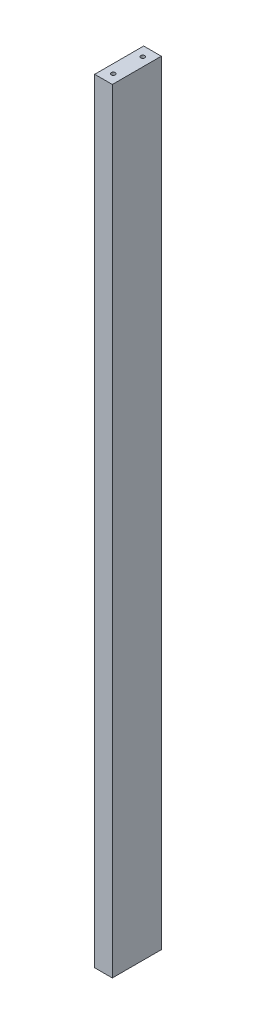
SolidWorks part; units mm, degrees
material "Beech"
ref_plane "Front Plane" through (0, 0, 0) normal (0, 0, 1) x (1, 0, 0)
ref_plane "Top Plane" through (0, 0, 0) normal (0, 1, 0) x (1, 0, 0)
ref_plane "Right Plane" through (0, 0, 0) normal (1, 0, 0) x (0, 0, -1)
sketch "Sketch1" plane through (0, 0, 0) normal (0, 1, 0) x (1, 0, 0)
  line L1 (0, 0) -> (18, 0)
  line L2 (0, 0) -> (0, 50)
  line L3 (0, 50) -> (18, 50)
  line L4 (18, 0) -> (18, 50)
  dimension "D1" = 18
  dimension "D2" = 50
extrude "base" add sketch "Sketch1" along normal blind 789.8
hole_wizard "end bolt holes for inserts" positions "Sketch2" profile "Sketch3" tap size "M5x0.8" standard "ANSI Metric"
sketch "Sketch2" plane through (0, 0, 0) normal (0, -1, 0) x (-1, 0, 0)
  line L1 (-9, 50) -> (-9, 0)
  line L2 (-18, 50) -> (0, 50) construction
  line L3 (0, 0) -> (-18, 0) construction
  line L4 (-9, 10) -> (-18, 25)
  line L5 (-18, 0) -> (-18, 50) construction
  line L6 (-18, 25) -> (-9, 40)
  point P10 (-9, 40)
  point P12 (-9, 10)
  dimension "D1" = 30
sketch "Sketch3" plane through (9, 0, -40) normal (1, 0, 0) x (0, 0, -1)
  line L0 (0, 0) -> (0, 15.2618)
  line L1 (0, 15.2618) -> (2.1, 14)
  line L2 (2.1, 14) -> (2.1, 0)
  line L5 (2.1, 0) -> (0, 0)
  line L10 (0, 15.2618) -> (-2.1, 14) construction
  line L11 (0, -6.35) -> (0, 107.95) construction
  dimension "Tap Drill Dia." = 4.2
  dimension "Tap Drill Depth" = 14
  dimension "Drill Angle" = 118
cosmetic thread "Hole Thread1" parameters "D1"=10, "D2"=5
cosmetic thread "Hole Thread2" parameters "D1"=10, "D2"=5
ref_plane "midplane along length" through (0, 394.9, 0) normal (0, -1, 0) x (-1, 0, 0)
mirror "mirror end bolt holes" about plane through (0, 394.9, 0) normal (0, -1, 0) of "end bolt holes for inserts"
equation "\"board_thickness\"= 18mm"
equation "\"way_width\"= 75mm"
equation "\"way_thickness\"= 50mm"
equation "\"radial_clearance\"= 0.1mm"
equation "\"slider_width\"= \"way_width\"-2* \"radial_clearance\""
equation "\"slider_thickness\"= \"way_thickness\" - 2 * \"radial_clearance\""
equation "\"column_width\"= \"way_width\" + 2 * \"board_thickness\""
equation "\"boxway_slot_width\"= 50mm"
equation "\"keeper_rail_width\"= (\"column_width\" - \"boxway_slot_width\")/2"
equation "\"slider_length\"= 125mm"
equation "\"nut_diameter\"= 22mm"
equation "\"nut_length\"= 15mm"
equation "\"leadscrew_diameter\"= 10mm"
equation "\"leadscrew_radial_clearance\"= 1mm"
equation "\"bearing_bolt_pattern_width\"= 35mm"
equation "\"bearing_bolt_pattern_height\"= 60mm"
equation "\"desktop_bolt_pattern_width\"= 30mm"
equation "\"desktop_bolt_pattern_height\"= 30mm"
equation "\"bearing_bolt_nut_counterbore_diameter\"= 12mm"
equation "\"bearing_bolt_nut_counterbore_depth\"= 10mm"
equation "\"desktop_depth\"= 500mm"
equation "\"desktop_width\"= 650mm"
equation "\"desktop_thickness\"= 18mm"
equation "\"leg_height\"=100mm"
equation "\"leg_width\"=18mm"
equation "\"leg_length\"=500mm"
equation "\"lap_joint_height\"= 50mm"
equation "\"lap_dowel_diameter\"= 8mm"
equation "\"lap_dowel_hole_z_spacing\"=30"
equation "\"D1@Sketch1\"=\"board_thickness\""
equation "\"D2@Sketch1\"=\"lap_joint_height\""
equation "\"D1@Sketch2\"=\"lap_dowel_hole_z_spacing\""
